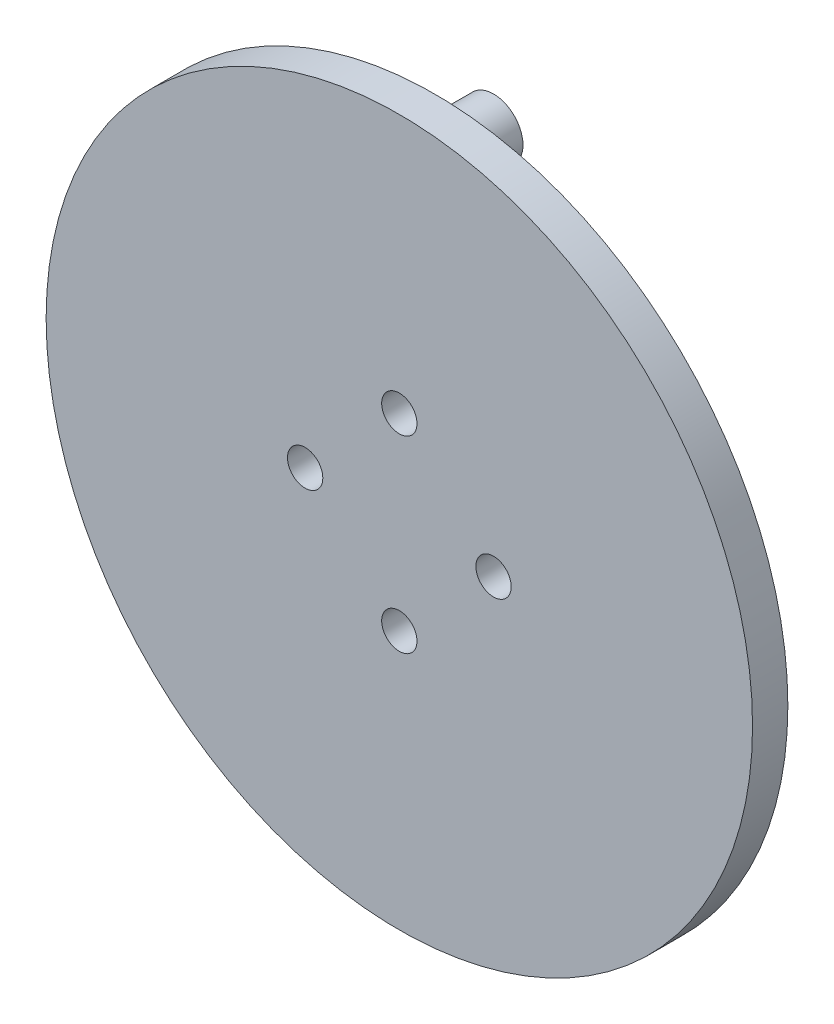
SolidWorks part; units mm, degrees
ref_plane "Front Plane" through (0, 0, 0) normal (0, 0, 1) x (1, 0, 0)
ref_plane "Top Plane" through (0, 0, 0) normal (0, 1, 0) x (1, 0, 0)
ref_plane "Right Plane" through (0, 0, 0) normal (1, 0, 0) x (0, 0, -1)
sketch "Sketch3" plane through (0, 0, 0) normal (0, 0, 1) x (1, 0, 0)
  circle A0 centre (0, 0) radius 30
  circle A1 centre (-8, 0) radius 1.5
  circle A2 centre (0, 8) radius 1.5
  circle A3 centre (8, 0) radius 1.5
  circle A4 centre (0, -8) radius 1.5
  point P14 (0, 0)
  dimension "D1" = 60
  dimension "D2" = 3
  dimension "D3" = 8
  dimension "D4" = 4
extrude "Boss-Extrude2" add sketch "Sketch3" along normal blind 3 contours A0 | A2 | A3 | A4 | A1
sketch "Sketch4" plane through (0, 0, 0) normal (0, 0, -1) x (-1, 0, 0)
  circle A0 centre (0, 25) radius 2.5
  dimension "D2" = 5
  dimension "D1" = 25
extrude "Boss-Extrude3" add sketch "Sketch4" along normal blind 5
sketch "Sketch5" plane through (0, 0, -5) normal (0, 0, -1) x (-1, 0, 0)
  line L0 (-2.5, 25) -> (2.5, 25) construction
  circle A0 centre (0, 25) radius 2.5 construction
  circle A1 centre (0, 25) radius 2.5 construction
ref_axis "Axis1" through (0, 25, -5) along (0, 0, 1)
ref_plane "Plane1" through (0, 25, 0) normal (0, 1, 0) x (1, 0, 0)
